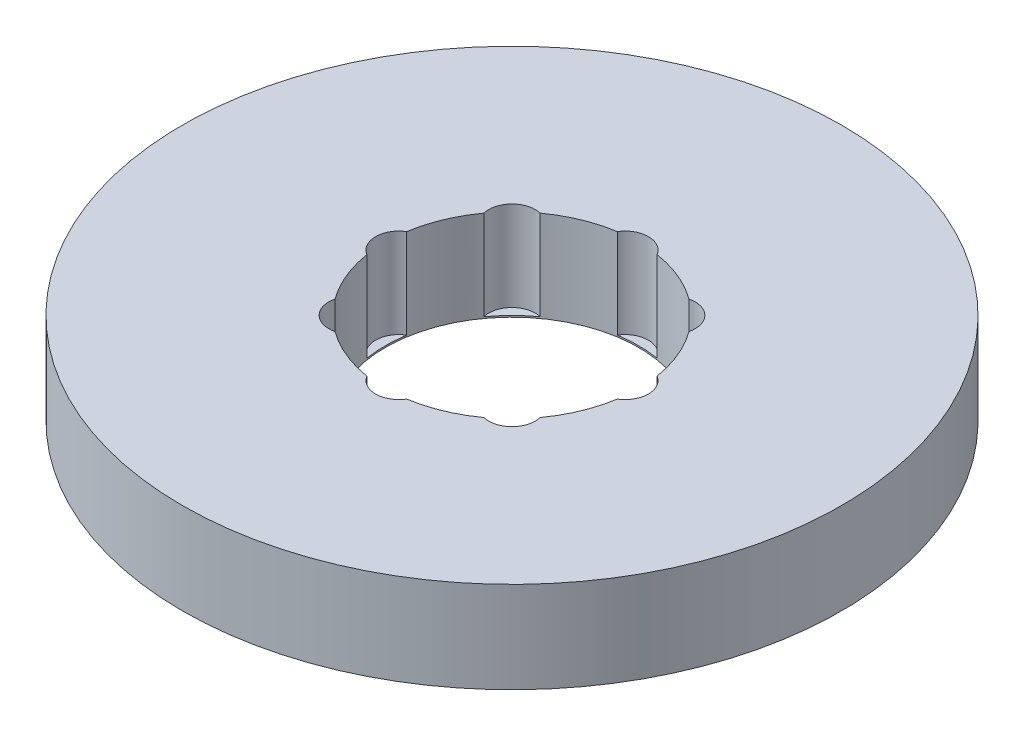
SolidWorks part; units mm, degrees
ref_plane "Front Plane" through (0, 0, 0) normal (0, 0, 1) x (1, 0, 0)
ref_plane "Top Plane" through (0, 0, 0) normal (0, 1, 0) x (1, 0, 0)
ref_plane "Right Plane" through (0, 0, 0) normal (1, 0, 0) x (0, 0, -1)
sketch "Sketch1" plane through (0, 0, 0) normal (0, 1, 0) x (1, 0, 0)
  circle A0 centre (0, 0) radius 32.5
  dimension "FLANGE_OD" = 65
extrude "Boss-Extrude1" add sketch "Sketch1" along normal blind 9
sketch "Sketch2" plane through (0, 0, 0) normal (0, 1, 0) x (1, 0, 0)
  circle A0 centre (0, 0) radius 12.5
  dimension "BORE_D" = 25
extrude "Cut-Extrude1" cut sketch "Sketch2" along normal through all
sketch "Sketch3" plane through (0, 9, 0) normal (0, 1, 0) x (1, 0, 0)
  circle A0 centre (0, 0) radius 11.155 construction
  circle A1 centre (-11.155, 0) radius 2.2933
  dimension "BOLT_D" = 4.5866
  dimension "BOLT_PCD" = 22.3099
extrude "Cut-Extrude2" cut sketch "Sketch3" against normal blind 8.8452
pattern_circular "CirPattern1" count 8 over 360 about axis through (0, 0, 0) along (0, 1, 0) of "Cut-Extrude2"
